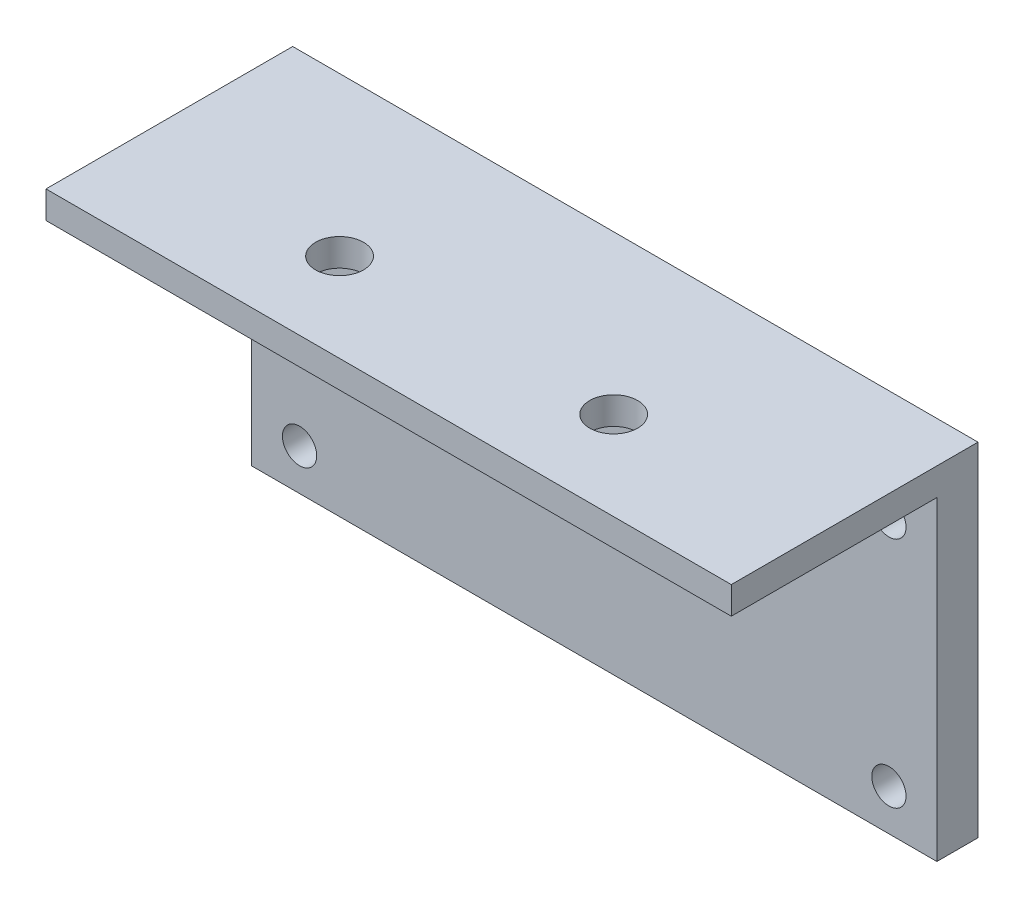
SolidWorks part; units mm, degrees
ref_plane "Front Plane" through (0, 0, 0) normal (0, 0, 1) x (1, 0, 0)
ref_plane "Top Plane" through (0, 0, 0) normal (0, 1, 0) x (1, 0, 0)
ref_plane "Right Plane" through (0, 0, 0) normal (1, 0, 0) x (0, 0, -1)
sketch "Sketch1" plane through (0, 0, 0) normal (0, 0, 1) x (1, 0, 0)
  line L1 (0, 0) -> (-50, 0)
  line L2 (0, 0) -> (0, 25)
  line L3 (0, 25) -> (-50, 25)
  line L4 (-50, 0) -> (-50, 25)
  dimension "D1" = 50
  dimension "D2" = 25
extrude "Boss-Extrude1" add sketch "Sketch1" along normal blind 3
sketch "Sketch3" plane through (0, 0, 3) normal (0, 0, 1) x (1, 0, 0)
  line L0 (0, -55) -> (0, 55) construction
  line L1 (-50, 25) -> (0, 25)
  line L2 (-50, 25) -> (-50, 23)
  line L3 (-50, 23) -> (0, 23)
  line L4 (0, 25) -> (0, 23)
  dimension "D1" = 2
extrude "Boss-Extrude2" add sketch "Sketch3" along normal blind 15
sketch "Sketch5" plane through (0, 0, 3) normal (0, 0, 1) x (1, 0, 0)
  circle A0 centre (-46.5001, 20.0092) radius 1.25
  circle A3 centre (-46.5001, 3.0092) radius 1.25
  circle A4 centre (-3.5001, 20.0092) radius 1.25
  circle A5 centre (-3.5001, 3.0092) radius 1.25
  point P4 (0, 0)
  point P5 (-46.9349, 20.2069)
  point P8 (-46.263, 20.7206)
  point P9 (0, 0)
  point P10 (-46.0259, 20.7602)
  point P13 (0, 0)
  point P14 (0, 0)
  point P15 (-46.5001, 20.0092)
  point P16 (0, 0)
  dimension "D1" = 43
  dimension "D2" = 2.5
  dimension "D3" = 17
  dimension "D4" = 17
extrude "Cut-Extrude1" cut sketch "Sketch5" against normal blind 15
sketch "Sketch6" plane through (0, 25, 0) normal (0, 1, 0) x (1, 0, 0)
  circle A0 centre (-35.0461, -11.5352) radius 1.75
  circle A1 centre (-15.0461, -11.5352) radius 1.75
  point P4 (0, 0)
  point P5 (0, 0)
  point P6 (0, 0)
  point P7 (0, 0)
  dimension "D1" = 3.5
  dimension "D2" = 20
extrude "Cut-Extrude2" cut sketch "Sketch6" against normal blind 15
